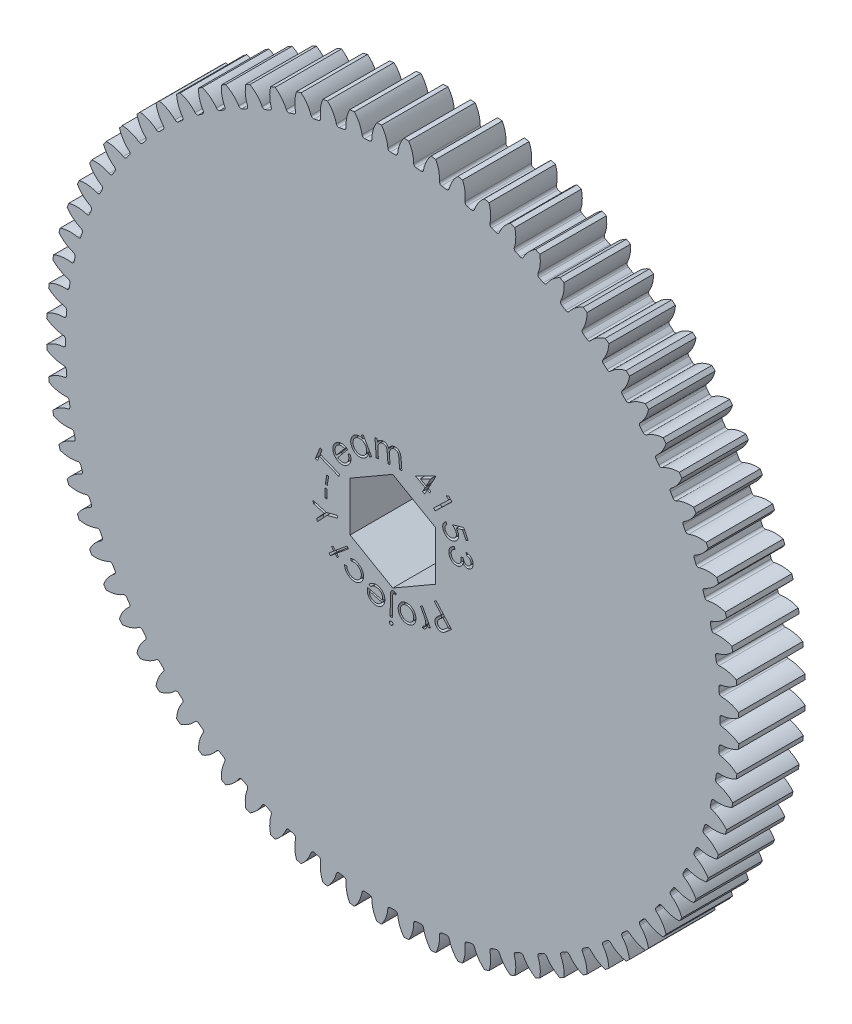
SolidWorks part; units mm, degrees
material "ABS"
ref_plane "Front Plane" through (0, 0, 0) normal (0, 0, 1) x (1, 0, 0)
ref_plane "Top Plane" through (0, 0, 0) normal (0, 1, 0) x (1, 0, 0)
ref_plane "Right Plane" through (0, 0, 0) normal (1, 0, 0) x (0, 0, -1)
sketch "Sketch1" plane through (0, 0, 0) normal (0, 0, 1) x (1, 0, 0)
  circle A0 centre (0, 0) radius 52.07
  circle A1 centre (0, 0) radius 5
  dimension "D1" = 104.14
  dimension "D2" = 10
extrude "Boss-Extrude1" add sketch "Sketch1" along normal mid plane 10
sketch "Sketch2" plane through (0, 0, 0) normal (0, 0, 1) x (1, 0, 0)
  line L0 (0, 0) -> (0, 52.07) construction
  line L1 (0, 0) -> (-0.7213, 49.2072) construction
  line L2 (0, 48.0084) -> (2.9386, 39.9346) construction
  arc A6 (0.7213, 49.2072) -> (-0.7213, 49.2072) centre (0, 0) ccw
  arc A7 (1.0124, 50.7899) -> (-1.0124, 50.7899) centre (0, 0) ccw construction
  circle A8 centre (0, 0) radius 52.07 construction
  arc A9 (1.6918, 52.0425) -> (-1.6918, 52.0425) centre (0, 0) ccw
  arc A10 (-0.7213, 49.2072) -> (-1.6918, 52.0425) centre (-5.5555, 49.1363) ccw
  arc A11 (0.7213, 49.2072) -> (1.6918, 52.0425) centre (5.5555, 49.1363) cw
  dimension "D1" = 101.6
  dimension "D2" = 2.8575
  dimension "D3" = 20
  dimension "D4" = 2.0249
extrude "Cut-Extrude1" cut sketch "Sketch2" against normal through all both and the other way through all
fillet "Fillet1" radius 0.381 2 edges at (0.7213, 49.2072, 0) (-0.7213, 49.2072, 0)
pattern_circular "CirPattern1" count 80 over 360 about axis through (0, 0, 5) along (0, 0, 1) of "Cut-Extrude1", "Fillet1"
sketch "Sketch4" plane through (0, 0, 5) normal (0, 0, 1) x (1, 0, 0)
  line L1 (6.4135, -3.7028) -> (6.4135, 3.7028)
  line L2 (6.4135, 3.7028) -> (0, 7.4057)
  line L3 (0, 7.4057) -> (-6.4135, 3.7028)
  line L4 (-6.4135, 3.7028) -> (-6.4135, -3.7028)
  line L5 (-6.4135, -3.7028) -> (0, -7.4057)
  line L6 (0, -7.4057) -> (6.4135, -3.7028)
  circle A0 centre (0, 0) radius 6.4135 construction
  dimension "D1" = 12.827
extrude "Cut-Extrude3" cut sketch "Sketch4" against normal through all both and the other way through all
sketch "Sketch5" plane through (0, 0, 5) normal (0, 0, 1) x (1, 0, 0)
  circle A0 centre (0, 0) radius 8.75 construction
  text T0 "Project Y--Team 4153"
  dimension "D1" = 17.5
extrude "Cut-Extrude4" cut sketch "Sketch5" against normal blind 1
equation "\"Module\"= 1.27"
equation "\"Bore\"= 10"
equation "\"Number of Teeth\"= 80"
equation "\"Pressure Angle\"= 20"
equation "\"D1@Sketch1\"=(\"Number of Teeth\"+2) * \"Module\""
equation "\"D2@Sketch1\"=\"Bore\""
equation "\"D1@CirPattern1\"=\"Number of Teeth\""
equation "\"D1@Sketch2\"=\"Number of Teeth\" * \"Module\""
equation "\"D2@Sketch2\"=if(\"Module\" < 1.25, 2.4 * \"Module\", 2.25 * \"Module\")"
equation "\"D3@Sketch2\"= \"Pressure Angle\""
equation "\"D4@Sketch2\"= (( PI * \"Module\") / 2) + .03 "
equation "\"D1@Fillet1\"=\"Module\" * 0.3"
